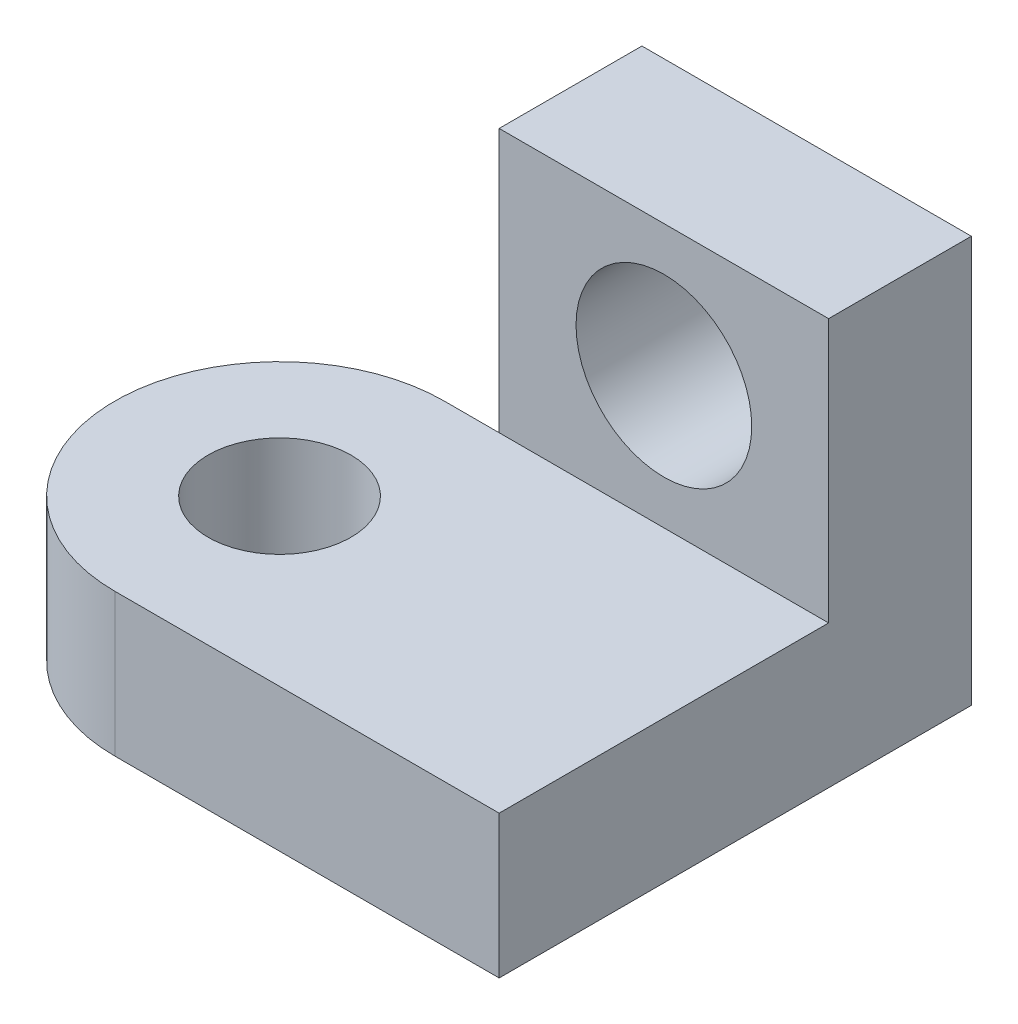
SolidWorks part; units mm, degrees
ref_plane "Front Plane" through (0, 0, 0) normal (0, 0, 1) x (1, 0, 0)
ref_plane "Top Plane" through (0, 0, 0) normal (0, 1, 0) x (1, 0, 0)
ref_plane "Right Plane" through (0, 0, 0) normal (1, 0, 0) x (0, 0, -1)
sketch "Sketch1" plane through (0, 0, 0) normal (0, 1, 0) x (1, 0, 0)
  line L1 (0, 0) -> (35, 0)
  line L2 (0, 0) -> (0, 30)
  line L3 (0, 30) -> (35, 30)
  line L4 (35, 0) -> (35, 30)
  line L9 (35, 30) -> (5, 30)
  line L10 (35, 30) -> (35, 43)
  line L11 (35, 43) -> (5, 43)
  line L12 (5, 30) -> (5, 43)
  circle A0 centre (0, 15) radius 6.5
  circle A1 centre (0, 15) radius 15
  dimension "D3" = 13
  dimension "D4" = 30
  dimension "D5" = 30
  dimension "D1" = 35
  dimension "D2" = 43
extrude "Boss-Extrude1" add sketch "Sketch1" along normal blind 13 contours L2 A1 A0 | L2 A1 A0 | A1 L1 L4 L3 region at (23.1491, 0, -15) region at (-7.2002, 0, -15) region at (7.2002, 0, -15)
extrude "Boss-Extrude2" add sketch "Sketch1<3>" along normal blind 37 contours L3 L11 region at (20, 0, -36.5)
sketch "Sketch1<3>" plane through (0, 0, 0) normal (0, 1, 0) x (1, 0, 0) same geometry as "Sketch1"
sketch "Sketch2" plane through (0, 0, -30) normal (0, 0, 1) x (1, 0, 0)
  circle A0 centre (20, 25) radius 8
  dimension "D3" = 16
  dimension "D1" = 15
  dimension "D2" = 12
extrude "Cut-Extrude1" cut sketch "Sketch2" against normal blind 37
